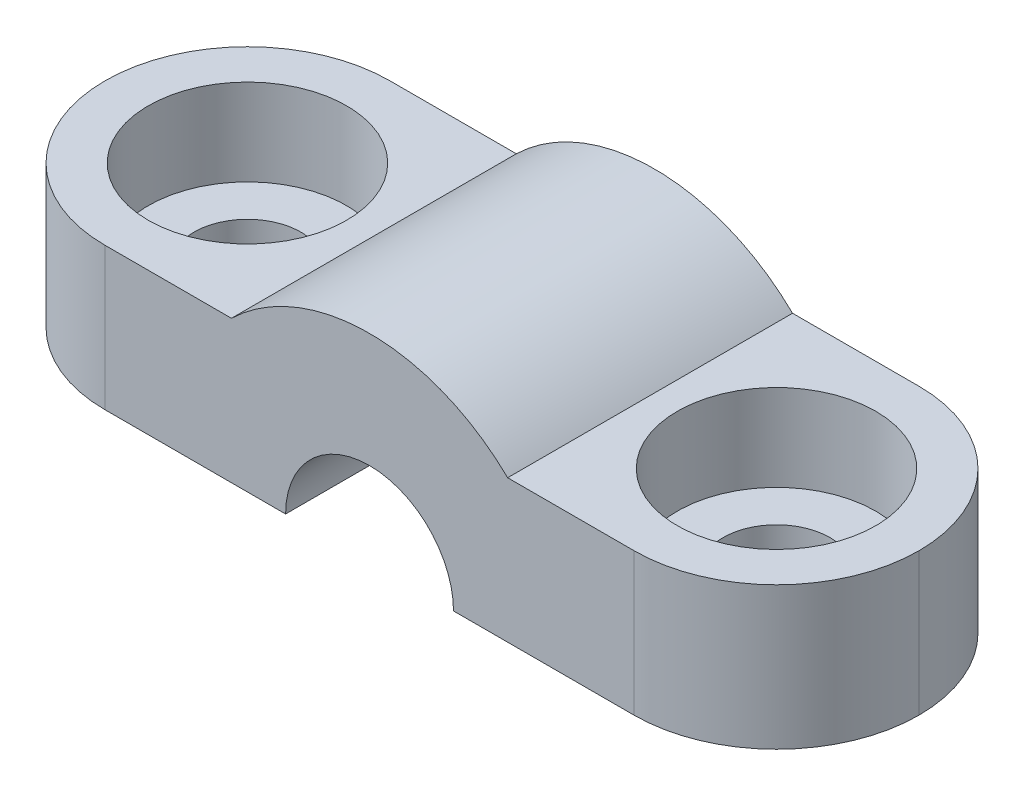
SolidWorks part; units mm, degrees
material "ABS"
ref_plane "Front Plane" through (0, 0, 0) normal (0, 0, 1) x (1, 0, 0)
ref_plane "Top Plane" through (0, 0, 0) normal (0, 1, 0) x (1, 0, 0)
ref_plane "Right Plane" through (0, 0, 0) normal (1, 0, 0) x (0, 0, -1)
ref_axis "Axis1" through (0, 0, 0) along (0, 0, 1)
sketch "Sketch1" plane through (0, 0, 0) normal (0, 1, 0) x (1, 0, 0)
  line L1 (-20, 7) -> (20, 7)
  line L2 (-20, 7) -> (-20, -7)
  line L3 (-20, -7) -> (20, -7)
  line L4 (20, 7) -> (20, -7)
  line L5 (-20, 7) -> (20, -7) construction
  line L6 (-20, -7) -> (20, 7) construction
  point P0 (0, 0)
  dimension "D1" = 14
  dimension "D2" = 40
extrude "Boss-Extrude1" add sketch "Sketch1" along normal blind 7
fillet "Fillet1" radius 7 4 edges at (-20, 3.5, 7) (20, 3.5, 7) (20, 3.5, -7) (-20, 3.5, -7)
sketch "Sketch2" plane through (0, 7, 0) normal (0, 1, 0) x (1, 0, 0)
  line L0 (0, 0) -> (0, 10.3236) construction
  circle A0 centre (-13, 0) radius 2.625
  circle A1 centre (13, 0) radius 2.625
  dimension "D1" = 5.25
extrude "Cut-Extrude1" cut sketch "Sketch2" against normal through all
sketch "Sketch3" plane through (0, 7, 0) normal (0, 1, 0) x (1, 0, 0)
  line L0 (0, 0) -> (0, 13.794) construction
  circle A0 centre (-13, 0) radius 4.875
  circle A1 centre (13, 0) radius 4.875
  dimension "D1" = 9.75
extrude "Cut-Extrude2" cut sketch "Sketch3" against normal blind 4.25
sketch "Sketch4" plane through (0, 0, 7) normal (0, 0, 1) x (1, 0, 0)
  line L0 (-13, 7) -> (13, 7) construction
  line L5 (13, 7) -> (-13, 7)
  line L6 (-13, 7) -> (-13, 0)
  line L7 (-13, 0) -> (13, 0)
  line L8 (13, 0) -> (13, 7)
  line L9 (6.7869, 7) -> (-6.7869, 7)
  arc A0 (6.7869, 7) -> (-6.7869, 7) centre (0, 0) ccw
  dimension "D1" = 9.75
  dimension "D2" = 0
extrude "Boss-Extrude2" add sketch "Sketch4" against normal up to surface (14 mm away) up to face at (0, 3.5, -7)
sketch "Sketch5" plane through (0, 0, 7) normal (0, 0, 1) x (1, 0, 0)
  line L0 (-13, 0) -> (13, 0) construction
  circle A0 centre (0, 0) radius 4.125
  dimension "D1" = 8.25
extrude "Cut-Extrude3" cut sketch "Sketch5" against normal through all
